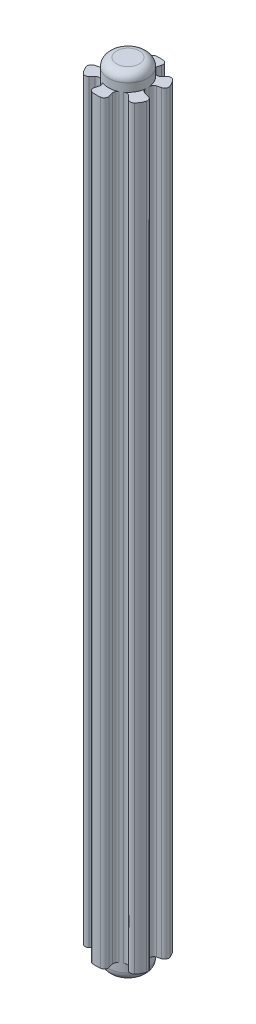
SolidWorks part; units mm, degrees
ref_plane "Front Plane" through (0, 0, 0) normal (0, 0, 1) x (1, 0, 0)
ref_plane "Top Plane" through (0, 0, 0) normal (0, 1, 0) x (1, 0, 0)
ref_plane "Right Plane" through (0, 0, 0) normal (1, 0, 0) x (0, 0, -1)
sketch "Sketch2" plane through (0, 0, 0) normal (0, 1, 0) x (1, 0, 0)
  line L0 (0, 0) -> (0.0739, 0)
  line L2 (2.3008, -0.5891) -> (3.7752, -0.9786)
  line L3 (0.0739, 0) -> (0.1042, -0.0303)
  line L4 (0, 0) -> (0.0858, -0.0446)
  line L5 (1.6802, 1.6786) -> (2.7413, 2.7388)
  line L6 (-1.6794, 1.6794) -> (-2.74, 2.74)
  line L8 (0.6147, 2.2941) -> (1.0029, 3.743)
  line L9 (-0.6147, 2.2941) -> (-1.0029, 3.743)
  line L10 (2.2941, 0.6147) -> (3.743, 1.0029)
  line L11 (0, 0) -> (0.1042, -0.0303)
  line L12 (-2.2941, 0.6147) -> (-3.743, 1.0029)
  line L13 (0.0739, 0) -> (0.0858, -0.0446)
  line L14 (-0.6147, -2.2941) -> (-1.0029, -3.743)
  line L15 (-2.2941, -0.6147) -> (-3.743, -1.0029)
  line L16 (-1.6794, -1.6794) -> (-2.74, -2.74)
  line L17 (0.6814, -2.2752) -> (1.0684, -3.7248)
  line L18 (1.7145, -1.6435) -> (2.7672, -2.6981)
  arc A0 (-2.2941, 0.6147) -> (-2.2941, -0.6147) centre (0, 0) ccw
  arc A1 (-2.74, 2.74) -> (-3.743, 1.0029) centre (0, 0) ccw
  arc A2 (1.0029, 3.743) -> (-1.0029, 3.743) centre (0, 0) ccw
  arc A3 (3.743, 1.0029) -> (2.7413, 2.7388) centre (0, 0) ccw
  arc A5 (-1.0029, -3.743) -> (1.0684, -3.7248) centre (0, 0) ccw
  arc A6 (-3.743, -1.0029) -> (-2.74, -2.74) centre (0, 0) ccw
  arc A7 (-2.74, 2.74) -> (-3.743, 1.0029) centre (0, 0) ccw
  arc A8 (1.0029, 3.743) -> (-1.0029, 3.743) centre (0, 0) ccw
  arc A9 (3.743, 1.0029) -> (2.7413, 2.7388) centre (0, 0) ccw
  arc A10 (-3.743, -1.0029) -> (-2.74, -2.74) centre (0, 0) ccw
  arc A11 (-1.0029, -3.743) -> (1.0684, -3.7248) centre (0, 0) ccw
  arc A12 (2.7672, -2.6981) -> (3.7752, -0.9786) centre (1.7753, -0.9614) ccw
  arc A13 (-0.6147, 2.2941) -> (-1.6794, 1.6794) centre (0, 0) ccw
  arc A14 (1.6802, 1.6786) -> (0.6147, 2.2941) centre (0, 0) ccw
  arc A15 (2.3008, -0.5891) -> (2.2941, 0.6147) centre (0, 0) ccw
  arc A16 (0.6814, -2.2752) -> (1.7145, -1.6435) centre (0, 0) ccw
  arc A17 (-1.6794, -1.6794) -> (-0.6147, -2.2941) centre (0, 0) ccw
  dimension "D1" = 3.875
  dimension "D2" = 2.375
extrude "Boss-Extrude1" add sketch "Sketch2" along normal blind 91.5 contours L16 A17 L14 A5 L17 A16 L18 A12 L2 A15 L10 A3 L5 A14 L8 A2 L9 A13 L6 A1 L12 A0 L15 A6 L11 L13 L4 L0 L3 region at (0.0225, 0, 0.0171)
sketch "Sketch3" plane through (0, 0, 0) normal (0, -1, 0) x (1, 0, 0)
  circle A0 centre (0, 0) radius 2.375
  dimension "D1" = 4.75
extrude "Boss-Extrude2" add sketch "Sketch3" along normal blind 2
sketch "Sketch4" plane through (0, 91.5, 0) normal (0, 1, 0) x (1, 0, 0)
  circle A0 centre (0, 0) radius 2.375
  dimension "D1" = 4.75
extrude "Boss-Extrude3" add sketch "Sketch4" along normal blind 2
fillet "Fillet1" radius 0.5 24 edges at (-2.74, 45.75, -2.74) (-1.6794, 45.75, -1.6794) (-0.6147, 45.75, -2.2941) (-1.0029, 45.75, -3.743) (1.0029, 45.75, -3.743) (0.6147, 45.75, -2.2941) (1.6802, 45.75, -1.6786) (2.7413, 45.75, -2.7388) (3.743, 45.75, -1.0029) (2.2941, 45.75, -0.6147) (2.3008, 45.75, 0.5891) (3.7752, 45.75, 0.9786) (2.7672, 45.75, 2.6981) (1.7145, 45.75, 1.6435) (0.6814, 45.75, 2.2752) (-1.6794, 45.75, 1.6794) (-2.2941, 45.75, 0.6147) (-2.2941, 45.75, -0.6147) (-0.6147, 45.75, 2.2941) (-3.743, 45.75, -1.0029) (-3.743, 45.75, 1.0029) (-2.74, 45.75, 2.74) (-1.0029, 45.75, 3.743) (1.0684, 45.75, 3.7248)
sketch "Sketch6" plane through (0, -2, 0) normal (0, -1, 0) x (1, 0, 0)
  circle A0 centre (0, 0) radius 1
  dimension "D1" = 2
extrude "Cut-Extrude4" cut sketch "Sketch6" against normal blind 0.5 draft 50
fillet "Fillet2" radius 1 2 edges at (0, 93.5, 2.375) (0, -2, -2.375)
